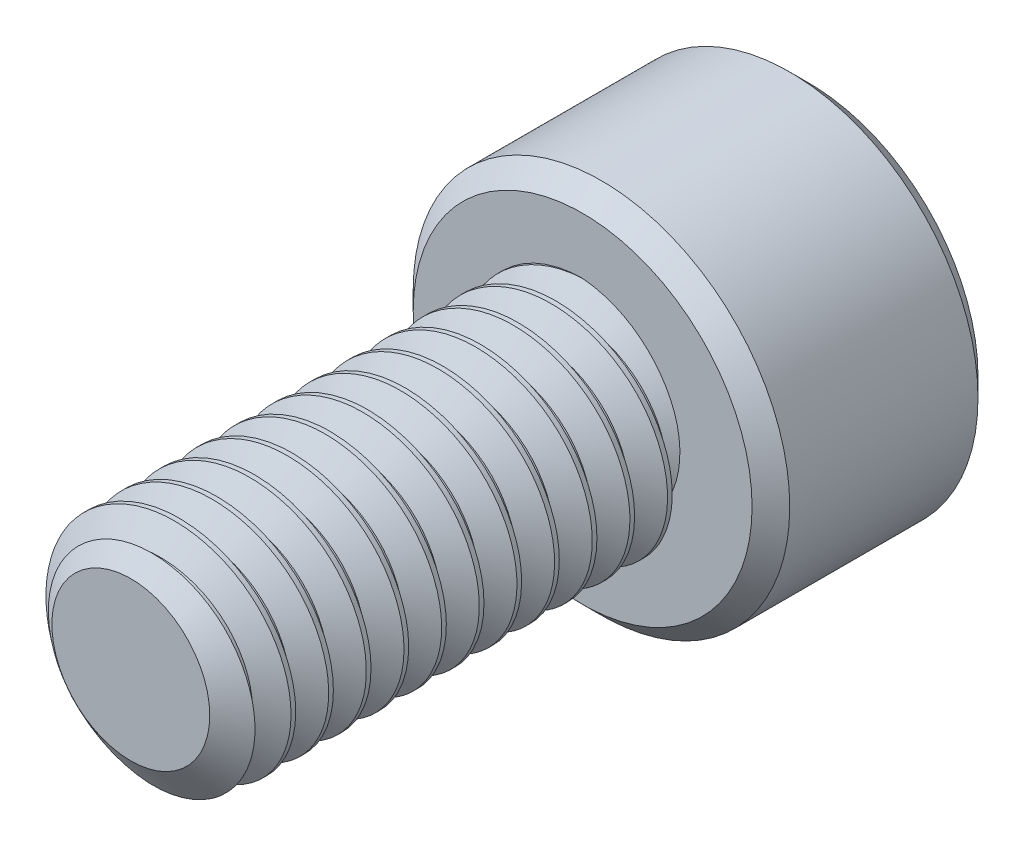
SolidWorks part; units mm, degrees
note: '?' marks a value the reader was unsure of.
other "DetailItem1"
ref_plane "Front Plane" through (0, 0, 0) normal (0, 0, 1) x (1, 0, 0)
ref_plane "Top Plane" through (0, 0, 0) normal (0, 1, 0) x (1, 0, 0)
ref_plane "Right Plane" through (0, 0, 0) normal (1, 0, 0) x (0, 0, -1)
sketch "Sketch1" plane through (0, 0, 0) normal (0, 0, 1) x (1, 0, 0)
  circle A0 centre (0, 0) radius 3
  dimension "OD" = 6
extrude "Extrude1" add sketch "Sketch1" against normal blind 12
sketch "Sketch2" plane through (0, 0, 0) normal (0, 0, 1) x (1, 0, 0)
  circle A0 centre (0, 0) radius 3 construction
  circle A1 centre (0, 0) radius 3
curve "Helix/Spiral1" pitch 1 height 13 turns 13 parameters "pitch"=1
sketch "Sketch3" plane through (0, 0, 0) normal (1, 0, 0) x (0, 0, -1)
  line L0 (-0.875, 3) -> (-0.5, 2.3505)
  line L1 (-0.5, 2.3505) -> (-0.375, 2.3505)
  line L2 (-0.375, 2.3505) -> (0, 3)
  line L3 (-0.875, 3) -> (0, 3)
  line L4 (-0.4375, 3) -> (-0.4375, 2.3505) construction
  line L5 (-0.6875, 2.6752) -> (-0.1875, 2.6752) construction
  line L6 (0, 3) -> (0, -3) construction
  dimension "D1" = 0.125
  dimension "D2" = 0.5
  dimension "D3" = 60
sweep "Cut-Sweep1" cut profiles "Sketch3" path "Helix/Spiral1"
sketch "Sketch4" plane through (0, 0, 0) normal (1, 0, 0) x (0, 0, -1)
  line L0 (0.6327, 3) -> (0, 2.0965)
  line L1 (0, 2.0965) -> (0, 3)
  line L2 (0.6327, 3) -> (0, 3)
  line L3 (-0.875, 3) -> (0, 3) construction
  line L4 (0, 0) -> (7.0209, 0) construction
  dimension "D1" = 55
  dimension "D2" = 0.254
revolve "Cut-Revolve1" cut sketch "Sketch4" angle 360 about L4
sketch "Sketch6" plane through (0, 0, -12) normal (0, 0, -1) x (-1, 0, 0)
  circle A0 centre (0, 0) radius 5
  dimension "head dia" = 10
extrude "Extrude2" add sketch "Sketch6" along normal blind 6
sketch "Sketch7" plane through (0, 0, -18) normal (0, 0, -1) x (-1, 0, 0)
  line L1 (0, 2.8868) -> (-2.5, 1.4434)
  line L2 (-2.5, 1.4434) -> (-2.5, -1.4434)
  line L3 (-2.5, -1.4434) -> (0, -2.8868)
  line L4 (0, -2.8868) -> (2.5, -1.4434)
  line L5 (2.5, -1.4434) -> (2.5, 1.4434)
  line L6 (2.5, 1.4434) -> (0, 2.8868)
  circle A0 centre (0, 0) radius 2.5 construction
  dimension "hex dia" = 5
extrude "Cut-Extrude1" cut sketch "Sketch7" against normal blind 3.75
sketch "Sketch8" plane through (0, 0, -18) normal (0, 0, -1) x (-1, 0, 0)
  circle A0 centre (0, 0) radius 2.8868
extrude "Cut-Extrude2" cut sketch "Sketch8" against normal through all draft 45
chamfer "Chamfer1" distance 0.5 angle 45 2 edges at (-5, 0, -18) (-5, 0, -12)
sketch "Sketch10" plane through (0, 0, -12) normal (0, 0, 1) x (1, 0, 0)
  circle A1 centre (0, 0) radius 3
  circle A2 centre (0, 0) radius 3
  dimension "D1" = 0
ref_plane "Plane1" through (0, 0, 0) normal (0, 0, 1) x (1, 0, 0)
extrude "partial thread" [suppressed] add sketch "Sketch10" along normal up to surface (31 mm away) separate body
chamfer "Chamfer2" [suppressed] distance 0.12 angle 45
combine bodies "Combine1" [suppressed] operation type? add bodies to combine 107 108
sketch "Sketch9" plane through (0, 0, 0) normal (1, 0, 0) x (0, 0, -1)
  line L0 (0, 3) -> (0, -3) construction
  line L1 (2.5, 3) -> (2.5, -3) construction
  dimension "D1" = 2.5
equation "\"D3@Helix/Spiral1\" = \"screw length@Extrude1\"+\"pitch@Helix/Spiral1\""
equation "\"D1@Sketch3\" = \"pitch@Helix/Spiral1\"*.125"
equation "\"D2@Sketch3\" = \"pitch@Helix/Spiral1\"*.5"
equation "\"D1@Cut-Extrude1\" = \"hex dia@Sketch7\"*.75"
equation "\"D1@Chamfer1\" = \"head dia@Sketch6\"*.05"
equation "\"D1@Sketch9\" = \"pitch@Helix/Spiral1\"*2.5"
equation "\"D1@Chamfer2\"=\"OD@Sketch1\"*.02"
